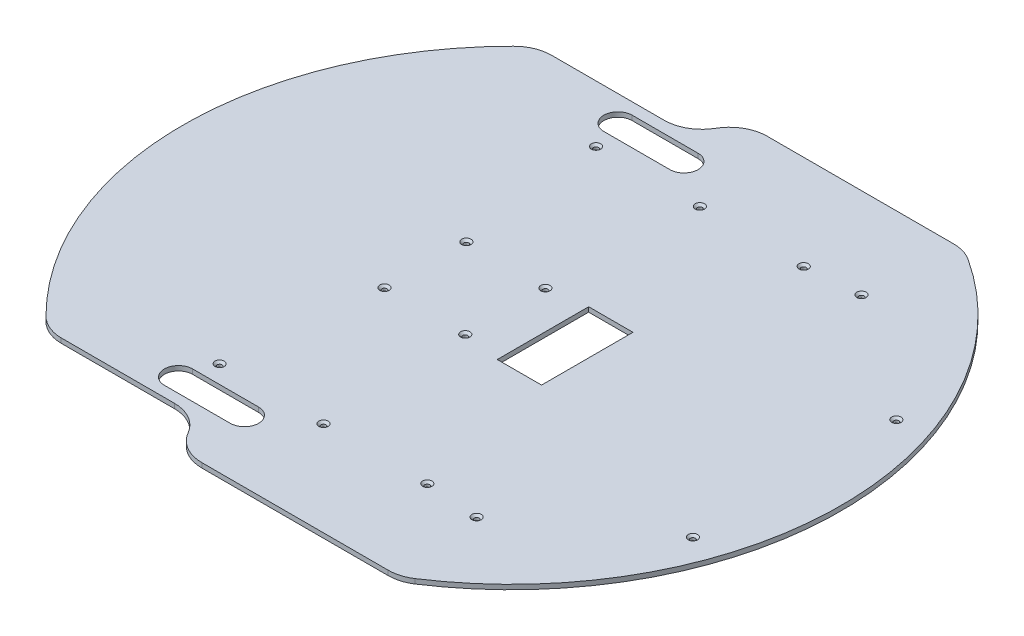
SolidWorks part; units mm, degrees
ref_plane "Plan de face" through (0, 0, 0) normal (0, 0, 1) x (1, 0, 0)
ref_plane "Plan de dessus" through (0, 0, 0) normal (0, 1, 0) x (1, 0, 0)
ref_plane "Plan de droite" through (0, 0, 0) normal (1, 0, 0) x (0, 0, -1)
sketch "Esquisse1" plane through (0, 0, 0) normal (0, 1, 0) x (1, 0, 0)
  line L0 (-138.94, 165.455) -> (-62.65, 165.455)
  line L5 (106.95, -190.145) -> (-18.65, -190.145)
  line L7 (-18.65, 190.855) -> (106.95, 190.855)
  line L8 (-138.94, -164.745) -> (-62.65, -164.745)
  arc A1 (-156.83, 157.725) -> (-138.94, 165.455) centre (-138.5811, 140.0575) cw
  arc A2 (-62.65, 165.455) -> (-40.65, 178.155) centre (-62.647, 190.855) ccw
  arc A3 (-40.65, 178.155) -> (-18.65, 190.855) centre (-18.653, 165.455) cw
  arc A4 (106.95, 190.855) -> (120.78, 186.755) centre (106.9427, 165.455) cw
  arc A5 (120.78, 186.755) -> (120.78, -186.045) centre (-0.716, 0.355) cw
  arc A6 (120.78, -186.045) -> (106.95, -190.145) centre (106.9427, -164.745) cw
  arc A7 (-18.65, -190.145) -> (-40.65, -177.445) centre (-18.653, -164.745) cw
  arc A8 (-40.65, -177.445) -> (-62.65, -164.745) centre (-62.647, -190.145) ccw
  arc A9 (-156.83, -157.015) -> (-138.94, -164.745) centre (-138.5811, -139.3475) ccw
  arc A10 (-156.83, 157.725) -> (-156.83, -157.015) centre (0.4625, 0.355) ccw
  point P0 (0, 0)
  point P25 (0, 0)
  point P26 (0, 0)
  point P28 (0, 0)
  dimension "D3" = 222.5
  dimension "D5" = 25.4
  dimension "D7" = 25.4
  dimension "D9" = 25.4
  dimension "D12" = 25.4
  dimension "D14" = 222.5
  dimension "D15" = 25.4
  dimension "D18" = 25.4
  dimension "D19" = 76.29
  dimension "D21" = 25.4
  dimension "D22" = 25.4
  dimension "D2" = 125.6
  dimension "D4" = 157.725
  dimension "D6" = 76.29
  dimension "D8" = 22
  dimension "D10" = 22
  dimension "D11" = 125.6
  dimension "D13" = 4.1
  dimension "D16" = 4.1
  dimension "D17" = 13.83
  dimension "D20" = 22
  dimension "D23" = 381
  dimension "D24" = 277.61
  dimension "D25" = 330.2
  dimension "D26" = 22
  dimension "D27" = 17.89
  dimension "D28" = 17.89
  dimension "D29" = 7.73
  dimension "D30" = 7.73
  dimension "D31" = 25.4
  dimension "D32" = 156.83
extrude "Boss.-Extru.1" add sketch "Esquisse1" along normal blind 3.18
sketch "Esquisse2" plane through (0, 3.18, 0) normal (0, 1, 0) x (1, 0, 0)
  line L0 (-76.45, -148.105) -> (-32, -148.105) construction
  line L1 (-76.45, -138.575) -> (-32, -138.575)
  line L2 (-76.45, -157.635) -> (-32, -157.635)
  line L3 (-138.94, -164.745) -> (-62.65, -164.745) construction
  line L4 (0, 0) -> (-294.8551, 0) construction
  line L5 (-76.45, 148.105) -> (-32, 148.105) construction
  line L6 (-76.45, 138.575) -> (-32, 138.575)
  line L7 (-76.45, 157.635) -> (-32, 157.635)
  line L8 (20.7, -30.425) -> (50.55, -30.425)
  line L9 (20.7, -30.425) -> (20.7, 31.175)
  line L10 (20.7, 31.175) -> (50.55, 31.175)
  line L11 (50.55, -30.425) -> (50.55, 31.175)
  arc A0 (-76.45, -138.575) -> (-76.45, -157.635) centre (-76.45, -148.105) ccw
  arc A1 (-32, -157.635) -> (-32, -138.575) centre (-32, -148.105) ccw
  arc A2 (-76.45, 138.575) -> (-76.45, 157.635) centre (-76.45, 148.105) cw
  arc A3 (-32, 157.635) -> (-32, 138.575) centre (-32, 148.105) cw
  point P2 (-54.225, -148.105)
  point P15 (-54.225, 148.105)
  point P21 (0, 0)
  dimension "D1" = 9.53
  dimension "D2" = 7.11
  dimension "D3" = 13.8
  dimension "D4" = 44.45
  dimension "D5" = 61.6
  dimension "D6" = 159.64
  dimension "D7" = 134.32
  dimension "D8" = 29.85
extrude "Enlèv. mat.-Extru.1" cut sketch "Esquisse2" against normal blind 3.18
sketch "Esquisse3" plane through (0, 3.18, 0) normal (0, 1, 0) x (1, 0, 0)
  line L1 (0.4625, 0.355) -> (-274.8168, 0.355) construction
  point P0 (-70.35, -126.475)
  point P1 (-0.37, -126.475)
  point P3 (69.61, -126.475)
  point P5 (105.7, -129.345)
  point P8 (190.32, -68.205)
  point P9 (0, 0)
  point P10 (190.32, 68.915)
  point P11 (105.7, 130.055)
  point P12 (69.61, 127.185)
  point P13 (-0.37, 127.185)
  point P14 (-70.35, 127.185)
  point P15 (0, 0)
  point P16 (0, 0)
  dimension "D1" = 12.1
  dimension "D2" = 6.1
  dimension "D3" = 69.98
  dimension "D4" = 69.98
  dimension "D5" = 2.87
  dimension "D6" = 36.09
  dimension "D7" = 84.62
  dimension "D8" = 61.14
hole_wizard "Fraisage pour vis à tête fraisée M31" positions "Esquisse3D2" profile "Esquisse8" countersink size "M3" standard "Ansi Metric" end condition through all
sketch3d "Esquisse3D2"
  point P0 (-70.35, 3.18, 126.475)
  point P3 (-0.37, 3.18, 126.475)
  point P6 (69.61, 3.18, 126.475)
  point P9 (105.7, 3.18, 129.345)
  point P12 (190.32, 3.18, 68.205)
  point P15 (190.32, 3.18, -68.915)
  point P18 (105.7, 3.18, -130.055)
  point P21 (69.61, 3.18, -127.185)
  point P24 (-0.37, 3.18, -127.185)
  point P27 (-70.35, 3.18, -127.185)
sketch "Esquisse8" plane through (-70.35, 3.18, 126.475) normal (1, 0, 0) x (0, 0, 1)
  line L0 (0, 0) -> (0, 3.18)
  line L1 (0, 3.18) -> (1.7, 3.18)
  line L2 (1.7, 3.18) -> (1.7, 1.45)
  line L3 (1.7, 1.45) -> (3.15, 0)
  line L5 (3.15, 0) -> (0, 0)
  line L6 (-1.7, 1.45) -> (-3.15, 0) construction
  line L11 (0, -6.35) -> (0, 107.95) construction
  dimension "Diamètre du perçage jusqu'au prochain" = 3.4
  dimension "Profondeur du perçage jusqu'au prochain" = 3.18
  dimension "Diamètre du fraisage entrant" = 6.3
  dimension "Angle du fraisage entrant" = 90
sketch "Esquisse9" plane through (0, 3.18, 0) normal (0, 1, 0) x (1, 0, 0)
  line L0 (20.7, 31.175) -> (20.7, -30.425) construction
  line L1 (-126.5546, 0.355) -> (63.971, -109.645) construction
  line L2 (63.971, -109.645) -> (63.971, 110.355) construction
  line L3 (63.971, 110.355) -> (-126.5546, 0.355) construction
  line L13 (-4.72, 27.445) -> (-4.72, -26.555) construction
  line L14 (-4.72, -26.555) -> (-59.23, -26.5244) construction
  line L15 (-59.23, -26.5244) -> (-58.3786, 27.829) construction
  line L16 (-58.3786, 27.829) -> (-4.72, 27.445) construction
  circle A0 centre (0.4625, 0.355) radius 63.5085 construction
  point P8 (0, 0)
  point P14 (0, 0)
  dimension "D2" = 54.36
  dimension "D1" = 220
  dimension "D3" = 54
  dimension "D4" = 3.73
  dimension "D5" = 25.42
  dimension "D6" = 53.66
  dimension "D7" = 54.51
  dimension "D8" = 90.41
  dimension "D9" = 90.487
hole_wizard "Fraisage pour vis à tête fraisée M32" positions "Esquisse3D3" profile "Esquisse10" countersink size "M3" standard "Ansi Metric" end condition through all
sketch3d "Esquisse3D3"
  point P0 (-59.23, 3.18, 26.5244)
  point P3 (-58.3786, 3.18, -27.829)
  point P6 (-4.72, 3.18, -27.445)
  point P9 (-4.72, 3.18, 26.555)
sketch "Esquisse10" plane through (-59.23, 3.18, 26.5244) normal (1, 0, 0) x (0, 0, 1)
  line L0 (0, 0) -> (0, 3.18)
  line L1 (0, 3.18) -> (1.7, 3.18)
  line L2 (1.7, 3.18) -> (1.7, 1.45)
  line L3 (1.7, 1.45) -> (3.15, 0)
  line L5 (3.15, 0) -> (0, 0)
  line L6 (-1.7, 1.45) -> (-3.15, 0) construction
  line L11 (0, -6.35) -> (0, 107.95) construction
  dimension "Diamètre du perçage jusqu'au prochain" = 3.4
  dimension "Profondeur du perçage jusqu'au prochain" = 3.18
  dimension "Diamètre du fraisage entrant" = 6.3
  dimension "Angle du fraisage entrant" = 90
